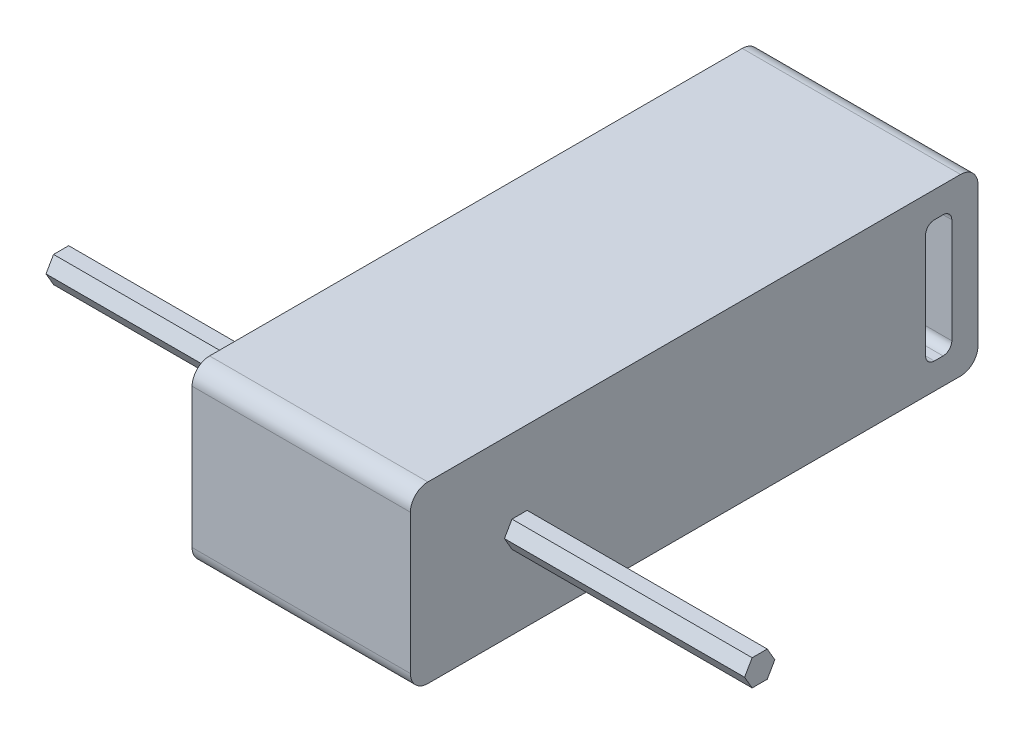
SolidWorks part; units mm, degrees
ref_plane "前视基准面" through (0, 0, 0) normal (0, 0, 1) x (1, 0, 0)
ref_plane "上视基准面" through (0, 0, 0) normal (0, 1, 0) x (1, 0, 0)
ref_plane "右视基准面" through (0, 0, 0) normal (1, 0, 0) x (0, 0, -1)
sketch "草图1" plane through (0, 0, 0) normal (1, 0, 0) x (0, 0, -1)
  line L0 (0, 0) -> (0, 20) construction
  line L1 (-32.5, 20) -> (32.5, 20)
  line L2 (32.5, 20) -> (32.5, 0)
  line L3 (32.5, 0) -> (-32.5, 0)
  line L4 (-32.5, 20) -> (-32.5, 0)
  dimension "D1" = 20
  dimension "D2" = 32.5
  dimension "D3" = 65
extrude "凸台-拉伸1" add sketch "草图1" along normal blind 25
fillet "圆角1" radius 2 1 edges at (12.5, 20, 32.5) type face fillet first side face at (12.5, 20, 0) second side face at (12.5, 10, 32.5)
fillet "圆角2" radius 2 1 edges at (12.5, 0, 32.5) type face fillet first side face at (12.5, 9, 32.5) second side face at (12.5, 0, 0)
fillet "圆角3" radius 2 1 edges at (12.5, 20, -32.5) type face fillet first side face at (12.5, 20, -1) second side face at (12.5, 10, -32.5)
fillet "圆角4" radius 2 1 edges at (12.5, 0, -32.5) type face fillet first side face at (12.5, 0, -1) second side face at (12.5, 9, -32.5)
ref_plane "基准面1" through (12.5, 0, 0) normal (-1, 0, 0) x (0, 0, 1)
sketch "草图3" plane through (12.5, 0, 0) normal (-1, 0, 0) x (0, 0, 1)
  line L5 (18.2679, 10) -> (19.134, 8.5)
  line L6 (19.134, 8.5) -> (20.866, 8.5)
  line L7 (20.866, 8.5) -> (21.7321, 10)
  line L8 (21.7321, 10) -> (20.866, 11.5)
  line L9 (20.866, 11.5) -> (19.134, 11.5)
  line L10 (19.134, 11.5) -> (18.2679, 10)
  dimension "D2" = 3
extrude "凸台-拉伸2" add sketch "草图3" along normal mid plane 80
ref_plane "基准面2" through (25, 0, 0) normal (1, 0, 0) x (0, 0, -1)
sketch "草图4" plane through (25, 0, 0) normal (-1, 0, 0) x (0, 0, 1)
  line L4 (-29.5, 4) -> (-29.5, 16)
  line L5 (-28.5, 17) -> (-27.5, 17)
  line L6 (-26.5, 16) -> (-26.5, 4)
  line L7 (-28.5, 3) -> (-27.5, 3)
  arc A0 (-28.5, 17) -> (-29.5, 16) centre (-28.5, 16) ccw
  arc A1 (-26.5, 16) -> (-27.5, 17) centre (-27.5, 16) ccw
  arc A2 (-28.5, 3) -> (-29.5, 4) centre (-28.5, 4) cw
  arc A3 (-26.5, 4) -> (-27.5, 3) centre (-27.5, 4) cw
  point P10 (-29.5, 17)
  point P13 (-26.5, 17)
  point P20 (-26.5, 10)
  dimension "D4" = 1
  dimension "D3" = 3
extrude "切除-拉伸1" cut sketch "草图4" along normal blind 5 contours L6 A3 L7 A2 L4 A0 L5 A1
mirror "镜向1" about plane through (12.5, 0, 0) normal (-1, 0, 0) of "切除-拉伸1"
sketch "草图5" plane through (12.5, 0, 0) normal (-1, 0, 0) x (0, 0, 1)
  line L0 (20, 11.5) -> (20, 8.5) construction
ref_plane "基准面3" through (0, 0, 20) normal (0, 0, -1) x (-1, 0, 0)
sketch "草图6" plane through (12.5, 0, 0) normal (-1, 0, 0) x (0, 0, 1)
  line L0 (18.2679, 10) -> (21.7321, 10) construction
ref_plane "基准面4" through (0, 10, 0) normal (0, 1, 0) x (1, 0, 0)
ref_axis "基准轴1" through (9.35, 10, 20) along (1, 0, 0)
